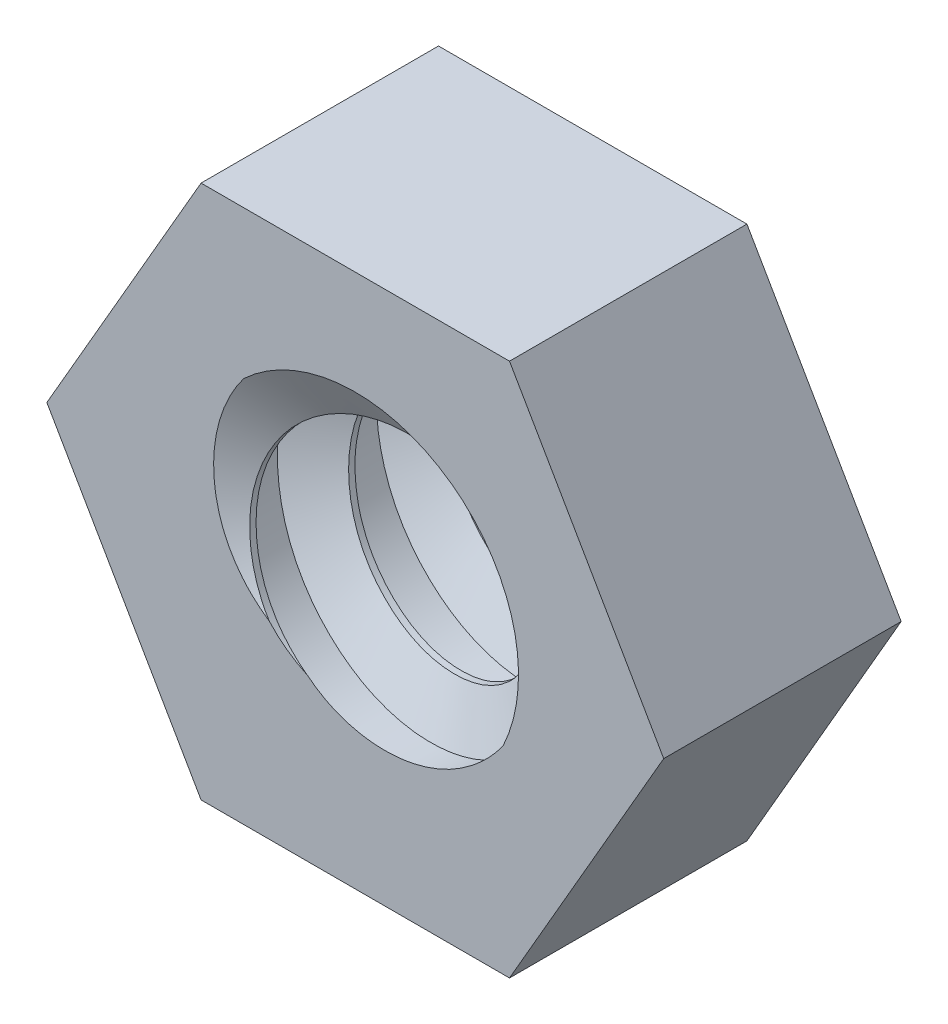
SolidWorks part; units mm, degrees
ref_plane "Front Plane" through (0, 0, 0) normal (0, 0, 1) x (1, 0, 0)
ref_plane "Top Plane" through (0, 0, 0) normal (0, 1, 0) x (1, 0, 0)
ref_plane "Right Plane" through (0, 0, 0) normal (1, 0, 0) x (0, 0, -1)
sketch "Sketch1" plane through (0, 0, 0) normal (0, 0, 1) x (1, 0, 0)
  line L0 (3.1177, 0) -> (1.5588, 2.7)
  line L1 (1.5588, 2.7) -> (-1.5588, 2.7)
  line L2 (-1.5588, 2.7) -> (-3.1177, 0)
  line L3 (-3.1177, 0) -> (-1.5588, -2.7)
  line L4 (-1.5588, -2.7) -> (1.5588, -2.7)
  line L5 (1.5588, -2.7) -> (3.1177, 0)
  circle A0 centre (0, 0) radius 1.175
extrude "Printed_nut_AF5p4_H2p4" add sketch "Sketch1" along normal blind 2.4 from offset 0
ref_plane "Actual_matching_female_P1_start_plane" through (0, 0, 0.25) normal (0, 0, 1) x (1, 0, 0)
sketch "Sketch2" plane through (0, 0, 0.25) normal (0, 0, 1) x (1, 0, 0)
  circle A0 centre (0, 0) radius 0.98
curve "Actual_matching_female_P1_helix" pitch 1 height 3 radius 0.98 centre (0, 0, 0.25) axis (0, 0, 1) start towards (1, 0, 0)
sketch3d "3DSketch1"
  line L0 (1.075, 0, -0.27) -> (1.65, 0, 0.03)
  line L1 (1.65, 0, 0.03) -> (1.65, 0, 0.47)
  line L2 (1.65, 0, 0.47) -> (1.075, 0, 0.7701)
  line L3 (1.075, 0, 0.7701) -> (1.075, 0, -0.27)
sweep "Actual_matching_female_P1" cut profiles "3DSketch1" path "Actual_matching_female_P1_helix" align with end faces yes
